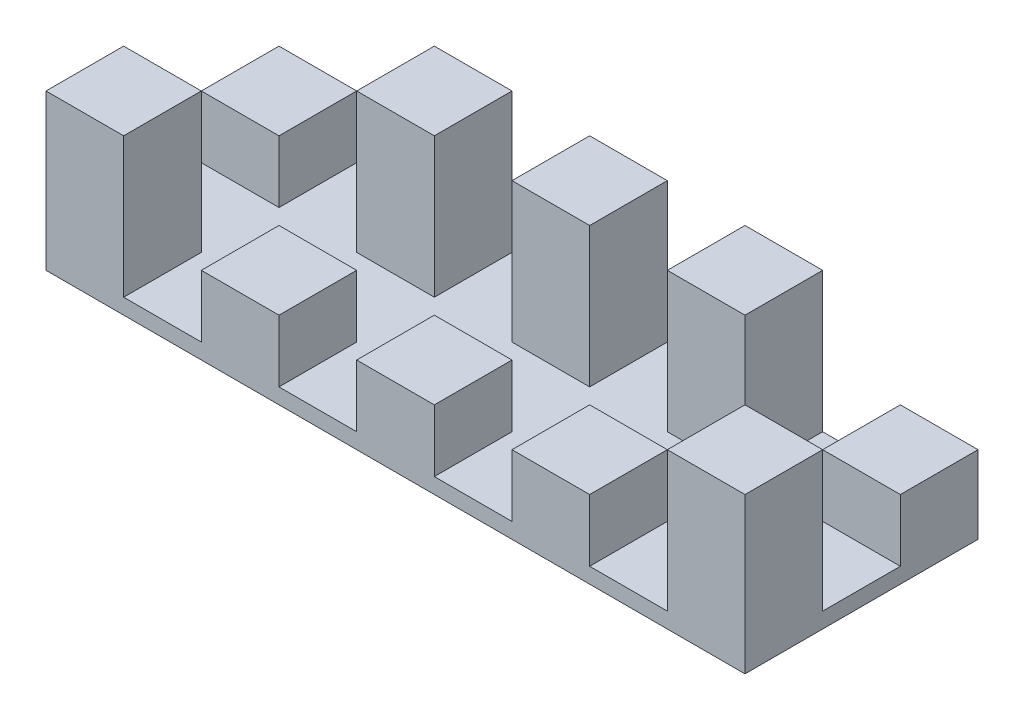
SolidWorks part; units mm, degrees
ref_plane "Front Plane" through (0, 0, 0) normal (0, 0, 1) x (1, 0, 0)
ref_plane "Top Plane" through (0, 0, 0) normal (0, 1, 0) x (1, 0, 0)
ref_plane "Right Plane" through (0, 0, 0) normal (1, 0, 0) x (0, 0, -1)
sketch "Sketch2" plane through (0, 0, 0) normal (0, 1, 0) x (1, 0, 0)
  line L0 (100, 150) -> (150, 150)
  line L1 (0, 150) -> (450, 150)
  line L2 (0, 150) -> (0, 0)
  line L3 (0, 0) -> (450, 0)
  line L4 (450, 150) -> (450, 0)
  line L5 (0, 150) -> (50, 150)
  line L6 (0, 150) -> (0, 100)
  line L7 (0, 100) -> (50, 100)
  line L8 (50, 150) -> (50, 100)
  line L9 (100, 150) -> (100, 100)
  line L10 (100, 100) -> (150, 100)
  line L11 (150, 150) -> (150, 100)
  line L12 (200, 150) -> (250, 150)
  line L13 (200, 150) -> (200, 100)
  line L14 (200, 100) -> (250, 100)
  line L15 (250, 150) -> (250, 100)
  line L16 (300, 150) -> (350, 150)
  line L17 (300, 150) -> (300, 100)
  line L18 (300, 100) -> (350, 100)
  line L19 (350, 150) -> (350, 100)
  line L20 (400, 150) -> (450, 150)
  line L21 (400, 150) -> (400, 100)
  line L22 (400, 100) -> (450, 100)
  line L23 (450, 150) -> (450, 100)
  line L24 (-64.313, 75) -> (520.8038, 75) construction
  line L25 (450, 0) -> (450, 50)
  line L26 (400, 50) -> (450, 50)
  line L27 (400, 0) -> (400, 50)
  line L28 (400, 0) -> (450, 0)
  line L29 (350, 0) -> (350, 50)
  line L30 (300, 50) -> (350, 50)
  line L31 (300, 0) -> (300, 50)
  line L32 (300, 0) -> (350, 0)
  line L33 (250, 0) -> (250, 50)
  line L34 (200, 50) -> (250, 50)
  line L35 (200, 0) -> (200, 50)
  line L36 (200, 0) -> (250, 0)
  line L37 (150, 0) -> (150, 50)
  line L38 (100, 50) -> (150, 50)
  line L39 (100, 0) -> (100, 50)
  line L40 (50, 0) -> (50, 50)
  line L41 (0, 50) -> (50, 50)
  line L42 (0, 0) -> (0, 50)
  line L43 (0, 0) -> (50, 0)
  line L44 (100, 0) -> (150, 0)
  point P0 (0, 0)
  point P49 (0, 0)
  dimension "D1" = 450
  dimension "D2" = 150
  dimension "D3" = 50
  dimension "D4" = 5
  dimension "D5" = 50
  dimension "D6" = 25
extrude "Boss-Extrude3" add sketch "Sketch2" along normal blind 10 contours L24 L2 L41 L40 L3 L39 L38 L37 L35 L34 L33 L31 L30 L29 L27 L26 L4 | L2 L24 L4 L22 L21 L1 L19 L18 L17 L15 L14 L13 L11 L10 L9 L8 L7 region at (95.4379, 0, -125) region at (225, 0, -70.4379)
extrude "Boss-Extrude4" add sketch "Sketch2<5>" along normal blind 100 contours L41 L2 L3 L40 | L11 L0 L9 L10 | L15 L1 L13 L14 | L19 L1 L17 L18 | L27 L3 L4 L26 region at (125, 0, -125) region at (225, 0, -125) region at (325, 0, -125) region at (25, 0, -25) region at (425, 0, -25)
sketch "Sketch2<5>" plane through (0, 0, 0) normal (0, 1, 0) x (1, 0, 0) same geometry as "Sketch2"
extrude "Boss-Extrude5" add sketch "Sketch2<6>" along normal blind 50 contours L8 L1 L2 L7 | L39 L3 L37 L38 | L21 L22 L4 L1 | L35 L34 L33 L36 | L31 L30 L29 L32 region at (25, 0, -125) region at (425, 0, -125) region at (125, 0, -25)
sketch "Sketch2<6>" plane through (0, 0, 0) normal (0, 1, 0) x (1, 0, 0) same geometry as "Sketch2"
